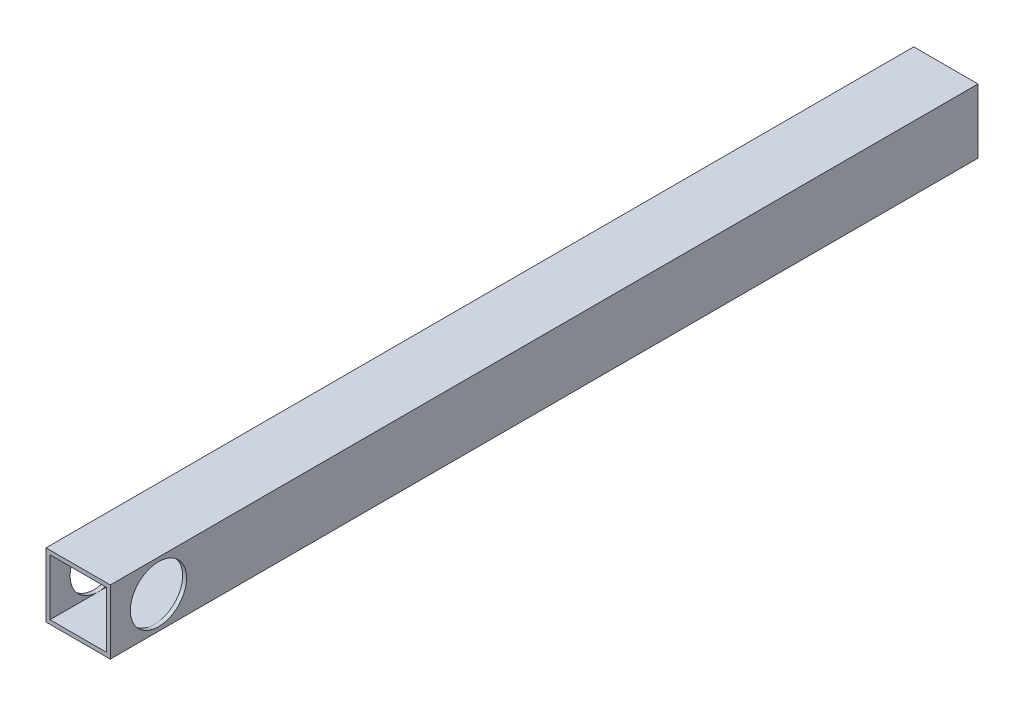
SolidWorks part; units mm, degrees
material "6061 Alloy"
ref_plane "Front Plane" through (0, 0, 0) normal (0, 0, 1) x (1, 0, 0)
ref_plane "Top Plane" through (0, 0, 0) normal (0, 1, 0) x (1, 0, 0)
ref_plane "Right Plane" through (0, 0, 0) normal (1, 0, 0) x (0, 0, -1)
sketch "Sketch1" plane through (0, 0, 0) normal (0, 0, 1) x (1, 0, 0)
  line L1 (12.7, -12.7) -> (-12.7, -12.7)
  line L2 (12.7, -12.7) -> (12.7, 12.7)
  line L3 (12.7, 12.7) -> (-12.7, 12.7)
  line L4 (-12.7, -12.7) -> (-12.7, 12.7)
  line L5 (12.7, -12.7) -> (-12.7, 12.7) construction
  line L6 (12.7, 12.7) -> (-12.7, -12.7) construction
  point P0 (0, 0)
  dimension "D1" = 25.4
extrude "Extrude-Thin1" add sketch "Sketch1" along normal blind 342.9 thin thin type one direction reverse wall 1.5875
sketch "Sketch2" plane through (12.7, 0, 0) normal (1, 0, 0) x (0, 0, -1)
  line L0 (-342.9, -12.7) -> (-342.9, 12.7) construction
  line L1 (-342.9, -12.7) -> (0, -12.7) construction
  circle A0 centre (-323.85, 0) radius 11.1125
  dimension "D1" = 22.225
  dimension "D2" = 19.05
  dimension "D3" = 12.7
extrude "Cut-Extrude1" cut sketch "Sketch2" against normal through all
